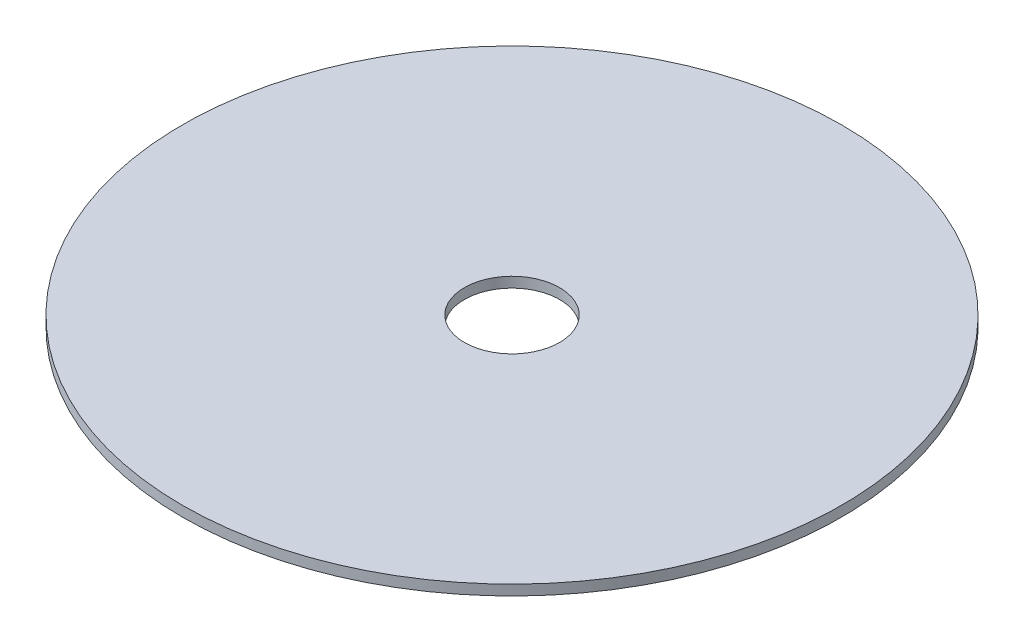
SolidWorks part; units mm, degrees
ref_plane "Front Plane" through (0, 0, 0) normal (0, 0, 1) x (1, 0, 0)
ref_plane "Top Plane" through (0, 0, 0) normal (0, 1, 0) x (1, 0, 0)
ref_plane "Right Plane" through (0, 0, 0) normal (1, 0, 0) x (0, 0, -1)
sketch "Sketch1" plane through (0, 0, 0) normal (0, 1, 0) x (1, 0, 0)
  line L1 (3.4946, -6.446) -> (7.3297, -0.1966) construction
  line L2 (7.3297, -0.1966) -> (3.8351, 6.2494) construction
  line L3 (3.8351, 6.2494) -> (-3.4946, 6.446) construction
  line L4 (-3.4946, 6.446) -> (-7.3297, 0.1966) construction
  line L5 (-7.3297, 0.1966) -> (-3.8351, -6.2494) construction
  line L6 (-3.8351, -6.2494) -> (3.4946, -6.446) construction
  circle A0 centre (0, 0) radius 50.8
  circle A1 centre (0, 0) radius 6.35 construction
  circle A2 centre (0, 0) radius 7.3323
  dimension "D1" = 12.7
  dimension "D2" = 101.6
base flange "Base-Flange1" sketch "Sketch1" thickness 1.5875 reverse thickness direction no parameters "D1"=254
sketch "Bend-Lines1" [suppressed] plane through (0, 0, 0) normal (0, 1, 0) x (1, 0, 0)
sketch "Bounding-Box1" [suppressed] plane through (0, 0, 0) normal (0, 1, 0) x (1, 0, 0)
sheet metal parameters "Sheet-Metal1" thickness 1.5875 parameters "D1"=254
flat pattern "Flat-Pattern1" [suppressed]
sketch "Bend-Lines2" plane through (0, 0, 0) normal (0, 1, 0) x (1, 0, 0)
sketch3d "Bounding-Box2" [suppressed]
  line L0 (-50.8571, -50.7428, 0) -> (50.7428, -50.8571, 0) construction
  line L1 (-50.7428, 50.8571, 0) -> (50.8571, 50.7428, 0) construction
  line L2 (-50.8571, -50.7428, 0) -> (-50.7428, 50.8571, 0) construction
  line L3 (50.7428, -50.8571, 0) -> (50.8571, 50.7428, 0) construction
